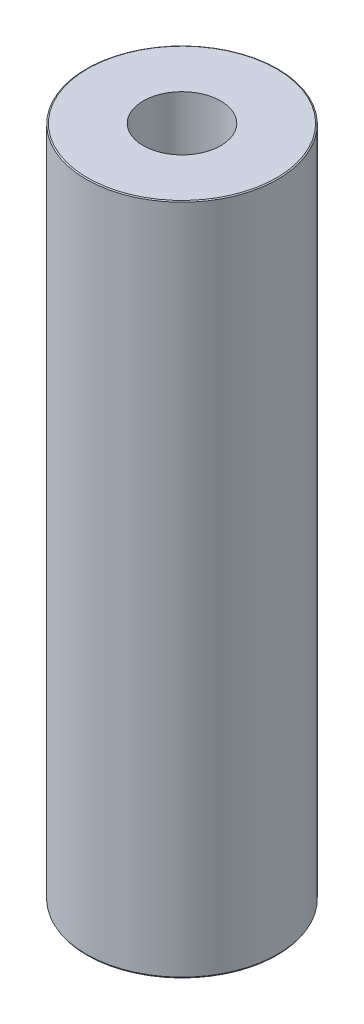
SolidWorks part; units mm, degrees
ref_plane "Front Plane" through (0, 0, 0) normal (0, 0, 1) x (1, 0, 0)
ref_plane "Top Plane" through (0, 0, 0) normal (0, 1, 0) x (1, 0, 0)
ref_plane "Right Plane" through (0, 0, 0) normal (1, 0, 0) x (0, 0, -1)
sketch "Sketch1" plane through (0, 0, 0) normal (0, 1, 0) x (1, 0, 0)
  circle A0 centre (0, 0) radius 60
  dimension "SHAFT_OD" = 120
extrude "Boss-Extrude1" add sketch "Sketch1" along normal blind 421.9844
sketch "Sketch2" plane through (0, 0, 0) normal (0, 1, 0) x (1, 0, 0)
  circle A0 centre (0, 0) radius 24.3066
  dimension "BORE_D" = 48.6131
extrude "Cut-Extrude1" cut sketch "Sketch2" along normal through all
chamfer "Chamfer1" distance 0.4335 angle 60 2 edges at (0, 421.9844, 60) (0, 0, 60) first distance on face at (0, 421.9844, 60) first distance on face at (0, 0, 24.3066)
